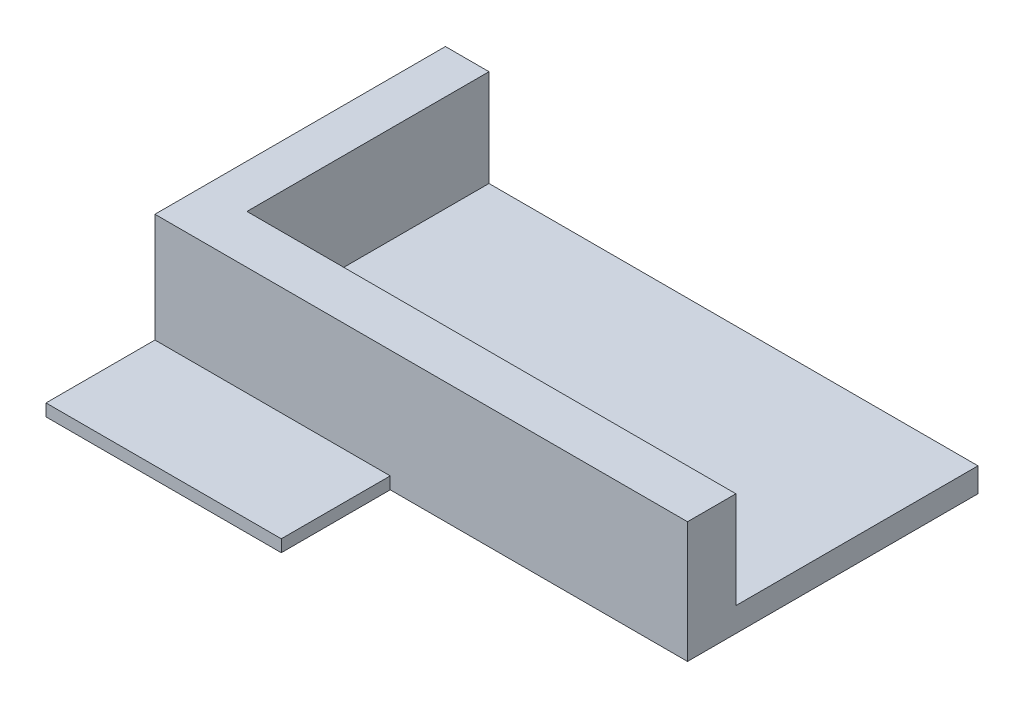
SolidWorks part; units mm, degrees
ref_plane "Front Plane" through (0, 0, 0) normal (0, 0, 1) x (1, 0, 0)
ref_plane "Top Plane" through (0, 0, 0) normal (0, 1, 0) x (1, 0, 0)
ref_plane "Right Plane" through (0, 0, 0) normal (1, 0, 0) x (0, 0, -1)
sketch "Sketch1" plane through (0, 0, 0) normal (0, 1, 0) x (1, 0, 0)
  line L0 (-69.85, -38.1) -> (69.85, -38.1)
  line L1 (-69.85, -38.1) -> (-69.85, 38.1)
  line L2 (69.85, -38.1) -> (69.85, 38.1)
  line L3 (-69.85, 38.1) -> (69.85, 38.1)
  line L4 (-69.85, -38.1) -> (69.85, 38.1) construction
  line L5 (69.85, -38.1) -> (-69.85, 38.1) construction
  line L10 (-58.42, -26.67) -> (58.42, 26.67) construction
  line L11 (58.42, -26.67) -> (-58.42, 26.67) construction
  point P1 (0, 0)
  point P2 (0, 0)
  dimension "D1" = 76.2
  dimension "D2" = 139.7
extrude "Boss-Extrude1" add sketch "Sketch1" along normal blind 31.75
sketch "Sketch2" plane through (0, 31.75, 0) normal (0, 1, 0) x (1, 0, 0)
  line L0 (-58.42, -25.4) -> (69.85, -25.4)
  line L1 (-58.42, -25.4) -> (-58.42, 38.1459)
  line L2 (69.85, -25.4) -> (69.85, 38.1459)
  line L3 (-58.42, 38.1459) -> (69.85, 38.1459)
  line L4 (69.85, -38.1) -> (69.85, 38.1) construction
  line L5 (-69.85, 38.1) -> (-69.85, -38.1) construction
  line L9 (-69.85, -38.1) -> (69.85, -38.1) construction
  dimension "D1" = 11.43
  dimension "D2" = 12.7
extrude "Cut-Extrude1" cut sketch "Sketch2" against normal blind 25.4
sketch "Sketch3" plane through (0, 6.35, 0) normal (0, 1, 0) x (1, 0, 0)
  line L0 (-58.42, -25.4) -> (-48.26, -25.4)
  line L1 (-58.42, -25.4) -> (-58.42, -15.24)
  line L2 (-48.26, -25.4) -> (-48.26, -15.24)
  line L3 (-58.42, -15.24) -> (-48.26, -15.24)
  line L4 (-58.42, -25.4) -> (69.85, -25.4) construction
  dimension "D1" = 10.16
  dimension "D2" = 10.16
extrude "Boss-Extrude3" add sketch "Sketch3" along normal blind 12.7
sketch "Sketch4" plane through (0, 19.05, 0) normal (0, 1, 0) x (1, 0, 0)
  line L0 (-48.26, -25.4) -> (-48.26, -15.24) construction
  line L1 (-48.26, -15.24) -> (-58.42, -15.24) construction
  circle A0 centre (-53.34, -20.32) radius 2.032
  point P4 (-48.26, -20.32)
  dimension "D1" = 4.064
  dimension "D2" = 5.08
  dimension "D3" = 5.08
extrude "Cut-Extrude2" cut sketch "Sketch4" against normal through all
sketch "Sketch5" plane through (0, 19.05, 0) normal (0, 1, 0) x (1, 0, 0)
  circle A0 centre (-53.34, -20.32) radius 3.937
extrude "Cut-Extrude3" cut sketch "Sketch5" against normal blind 2.286
sketch "Sketch6" plane through (0, 0, 38.1) normal (0, 0, 1) x (1, 0, 0)
  line L1 (-69.85, 0) -> (-8.128, 0)
  line L2 (-69.85, 0) -> (-69.85, 3.175)
  line L3 (-69.85, 3.175) -> (-8.128, 3.175)
  line L4 (-8.128, 0) -> (-8.128, 3.175)
  dimension "D1" = 61.722
  dimension "D2" = 3.175
extrude "Boss-Extrude4" add sketch "Sketch6" along normal blind 28.575
